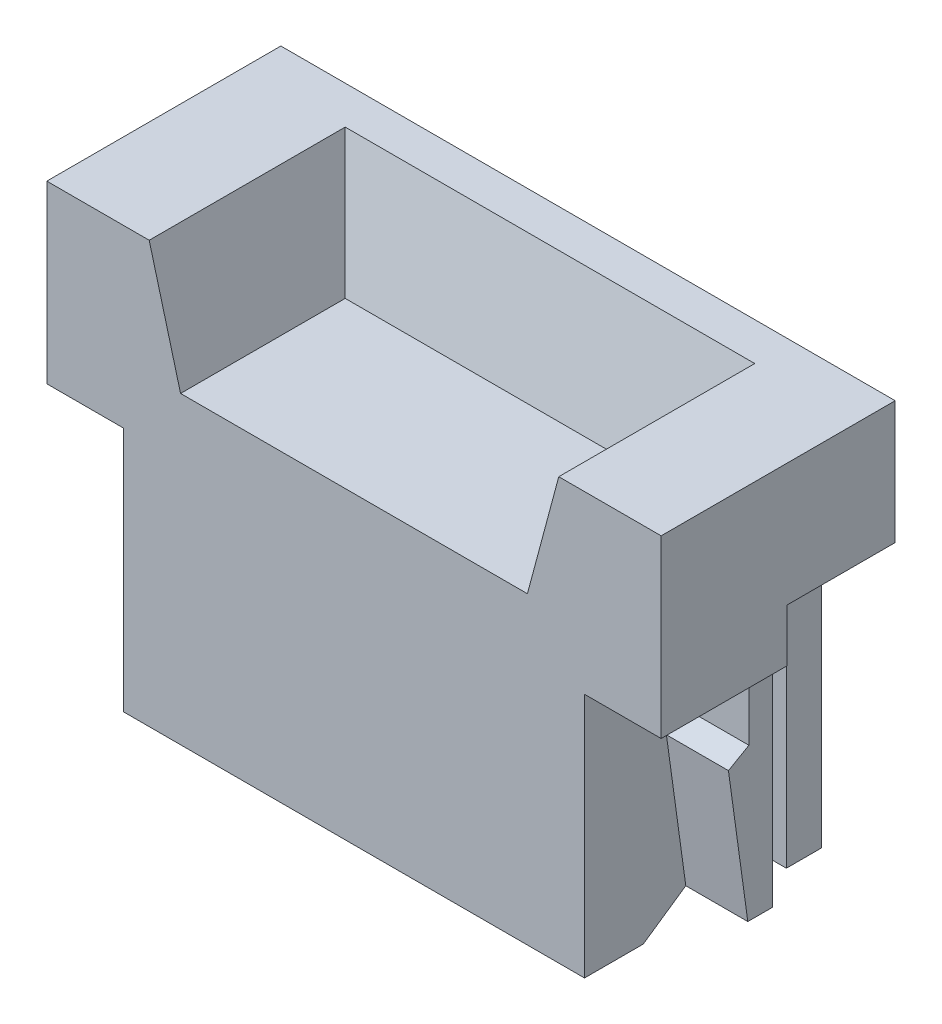
SolidWorks part; units mm, degrees
ref_plane "Front Plane" through (0, 0, 0) normal (0, 0, 1) x (1, 0, 0)
ref_plane "Top Plane" through (0, 0, 0) normal (0, 1, 0) x (1, 0, 0)
ref_plane "Right Plane" through (0, 0, 0) normal (1, 0, 0) x (0, 0, -1)
sketch "Sketch1" plane through (0, 0, 0) normal (1, 0, 0) x (0, 0, -1)
  line L0 (76.1908, 253.9388) -> (293.5266, 253.9388) construction
  line L1 (23.1526, 131.5086) -> (115.714, 131.5086) construction
  line L2 (4, 7.1) -> (1.0928, 7.1)
  line L3 (0, 0) -> (4, 0) construction
  line L4 (0, 0) -> (0, 7.1) construction
  line L5 (0, 7.1) -> (4, 7.1) construction
  line L6 (4, 0) -> (4, 7.1) construction
  line L7 (1.0928, 7.1) -> (1.0928, 6.4991)
  line L8 (1.0928, 6.4991) -> (0, 6.4991)
  line L9 (0, 6.4991) -> (0, 0)
  line L10 (0, 0) -> (1.0042, 0)
  line L11 (1.0042, 0) -> (1.7309, 0.4997)
  line L12 (1.7309, 0.4997) -> (3.45, 0.4997)
  line L13 (3.45, 0.4997) -> (3.45, 5.8996)
  line L14 (3.45, 5.8996) -> (4, 5.8996)
  line L15 (4, 5.8996) -> (4, 7.1)
  point P9 (1.0042, 0)
  point P18 (1.7006, 0.4997)
  dimension "D1" = 7.1
  dimension "D2" = 4
  dimension "D3" = 1.2004
  dimension "D4" = 3.45
  dimension "D5" = 5.3998
  dimension "D6" = 1.0042
  dimension "D7" = 1.7191
  dimension "D8" = 2.9072
  dimension "D9" = 0.6009
extrude "Boss-Extrude1" add sketch "Sketch1" along normal mid plane 10
sketch "Sketch2" plane through (0, 7.1, 0) normal (0, 1, 0) x (1, 0, 0)
  line L0 (-6, 4) -> (-4.54, 4)
  line L1 (5, 4) -> (-5, 4) construction
  line L2 (-4.54, 4) -> (-4.54, 2.85)
  line L3 (-4.54, 2.85) -> (-3.94, 2.85)
  line L4 (-3.94, 2.85) -> (-3.94, 2.15)
  line L5 (-3.94, 2.15) -> (-5, 2.15)
  line L6 (-5, 4) -> (-5, 1.0928) construction
  line L7 (-5, 2.15) -> (-5, 1.75)
  line L8 (-5, 1.75) -> (-3.94, 1.75)
  line L9 (-3.94, 1.75) -> (-3.94, 0)
  line L10 (5, 0) -> (-5, 0) construction
  line L11 (-3.94, 0) -> (-6, 0)
  line L12 (-6, 0) -> (-6, 4)
  line L13 (5, 3.45) -> (-5, 3.45) construction
  line L14 (0, 0) -> (0, 4) construction
  line L15 (6, 0) -> (6, 4)
  line L16 (3.94, 0) -> (6, 0)
  line L17 (3.94, 1.75) -> (3.94, 0)
  line L18 (5, 1.75) -> (3.94, 1.75)
  line L19 (5, 2.15) -> (5, 1.75)
  line L20 (3.94, 2.15) -> (5, 2.15)
  line L21 (3.94, 2.85) -> (3.94, 2.15)
  line L22 (4.54, 2.85) -> (3.94, 2.85)
  line L23 (4.54, 4) -> (4.54, 2.85)
  line L24 (6, 4) -> (4.54, 4)
  dimension "D1" = 4.54
  dimension "D2" = 3.94
  dimension "D3" = 1.75
  dimension "D4" = 1
  dimension "D5" = 0.4
  dimension "D6" = 0.6
extrude "Cut-Extrude1" cut sketch "Sketch2" against normal through all
sketch "Sketch3" plane through (0, 0.4997, 0) normal (0, -1, 0) x (1, 0, 0)
  line L0 (4.54, -3.45) -> (-4.54, -3.45) construction
  line L1 (-0.45, -1.9) -> (0.45, -1.9)
  line L2 (-0.45, -1.9) -> (-0.45, -2.8)
  line L3 (-0.45, -2.8) -> (0.45, -2.8)
  line L4 (0.45, -1.9) -> (0.45, -2.8)
  line L5 (2.05, -1.9) -> (2.05, -2.8)
  line L6 (2.05, -1.9) -> (2.95, -1.9)
  line L7 (2.95, -1.9) -> (2.95, -2.8)
  line L8 (2.05, -2.8) -> (2.95, -2.8)
  line L9 (-2.95, -1.9) -> (-2.95, -2.8)
  line L10 (-2.95, -1.9) -> (-2.05, -1.9)
  line L11 (-2.05, -1.9) -> (-2.05, -2.8)
  line L12 (-2.95, -2.8) -> (-2.05, -2.8)
  point P6 (0, -2.8)
  dimension "D1" = 0.65
  dimension "D2" = 0.9
  dimension "D5" = 2.5
  dimension "D6" = 2.5
  dimension "D3" = 2
  dimension "D4" = 2
extrude "Cut-Extrude2" cut sketch "Sketch3" against normal through all
sketch "Sketch4" plane through (3.94, 0, 0) normal (1, 0, 0) x (0, 0, -1)
  line L0 (1.75, 0.4997) -> (1.7309, 0.4997)
  line L1 (1.7309, 0.4997) -> (1.4, 2.8997)
  line L2 (1.4, 2.8997) -> (1.75, 3.0997)
  line L3 (1.75, 0.4997) -> (1.75, 7.1) construction
  line L4 (1.75, 3.0997) -> (1.75, 0.4997)
  line L5 (2.15, 7.1) -> (2.15, 0.4997) construction
  point P10 (1.4, 2.8872)
  dimension "D1" = 0.75
  dimension "D2" = 2.6
  dimension "D3" = 2.4
extrude "Boss-Extrude2" add sketch "Sketch4" along normal through all and the other way through all
sketch "Sketch5" plane through (0, 0.4997, 0) normal (0, -1, 0) x (1, 0, 0)
  line L0 (-1.55, -3.45) -> (-1.25, -3.15)
  line L1 (4.54, -3.45) -> (-4.54, -3.45) construction
  line L2 (-1.25, -3.15) -> (-0.95, -3.45)
  line L3 (-0.95, -3.45) -> (-1.55, -3.45)
  line L8 (0, 0) -> (0, -3.45) construction
  line L9 (0.95, -3.45) -> (1.55, -3.45)
  line L10 (1.25, -3.15) -> (0.95, -3.45)
  line L11 (1.55, -3.45) -> (1.25, -3.15)
  dimension "D1" = 2.5
  dimension "D2" = 0.6
extrude "Cut-Extrude3" cut sketch "Sketch5" against normal up to surface (5.3998 mm away) up to face at (0, 5.8996, -3.725)
sketch "Sketch6" plane through (0, 7.1, 0) normal (0, 1, 0) x (1, 0, 0)
  line L0 (4.54, 4) -> (-4.54, 4) construction
  line L1 (5, 4) -> (-5, 4)
  line L2 (5, 4) -> (5, 0)
  line L3 (5, 0) -> (-5, 0)
  line L4 (-5, 4) -> (-5, 0)
  point P4 (5.1362, 4.2959)
extrude "Boss-Extrude3" add sketch "Sketch6" against normal blind 2 and the other way blind 0.1
sketch "Sketch7" plane through (0, 7.2, 0) normal (0, 1, 0) x (1, 0, 0)
  line L1 (-2.95, 2.8) -> (2.95, 2.8) construction
  line L2 (-2.95, 2.8) -> (-2.95, 1.9) construction
  line L3 (-2.95, 1.9) -> (2.95, 1.9) construction
  line L4 (2.95, 2.8) -> (2.95, 1.9) construction
  line L8 (-3.5, 3.35) -> (-2.05, 1.9) construction
  line L9 (-3.5, 3.35) -> (3.5, 3.35)
  line L10 (-3.5, 3.35) -> (-3.5, 1.35)
  line L11 (-3.5, 1.35) -> (3.5, 1.35)
  line L12 (3.5, 3.35) -> (3.5, 1.35)
  point P4 (0, 3.35)
  point P6 (-2.05, 1.9)
  point P12 (-3.5, 2.35)
  point P13 (-2.95, 2.35)
  point P15 (0, 0)
  dimension "D2" = 2
extrude "Cut-Extrude4" cut sketch "Sketch7" against normal blind 2 draft 15
sketch "Sketch8" plane through (0, 0, 0) normal (0, 0, 1) x (1, 0, 0)
  line L4 (-2.9641, 5.2) -> (2.9641, 5.2)
  line L5 (-3.5, 7.2) -> (-2.9641, 5.2)
  line L6 (3.5, 7.2) -> (-3.5, 7.2)
  line L7 (2.9641, 5.2) -> (3.5, 7.2)
  line L9 (-3.5, 7.2) -> (-2.9641, 5.2)
  line L10 (3.5, 7.2) -> (-3.5, 7.2)
  line L11 (2.9641, 5.2) -> (3.5, 7.2)
  line L12 (-2.9641, 5.2) -> (2.9641, 5.2)
  dimension "D1" = 0
extrude "Cut-Extrude5" cut sketch "Sketch8" against normal up to surface (1.35 mm away) up to face at (0, 6.2, -1.6179)
sketch "Sketch9" plane through (0, 5.1, 0) normal (0, -1, 0) x (1, 0, 0)
  line L0 (-5, -1.75) -> (-3.94, -1.75) construction
  line L1 (-3.94, -1.75) -> (-3.94, 0) construction
  line L2 (-3.94, 0) -> (-5, 0) construction
  line L3 (-5, 0) -> (-5, -1.75) construction
  line L4 (3.94, 0) -> (3.94, -1.75) construction
  line L5 (3.94, -1.75) -> (5, -1.75) construction
  line L6 (5, -1.75) -> (5, 0) construction
  line L7 (5, 0) -> (3.94, 0) construction
  line L8 (-5, -1.75) -> (-3.94, -1.75)
  line L9 (-3.94, -1.75) -> (-3.94, 0)
  line L10 (-3.94, 0) -> (-5, 0)
  line L11 (-5, 0) -> (-5, -1.75)
  line L12 (3.94, 0) -> (3.94, -1.75)
  line L13 (3.94, -1.75) -> (5, -1.75)
  line L14 (5, -1.75) -> (5, 0)
  line L15 (5, 0) -> (3.94, 0)
extrude "Boss-Extrude4" add sketch "Sketch9" along normal blind 0.9
ref_axis "Axis1" through (5, 7.2, 0) along (-1, 0, 0)
ref_point "Point2"
sketch "Sketch10" plane through (5, 0, 0) normal (1, 0, 0) x (0, 0, -1)
  line L0 (0, 4.2) -> (2.15, 4.2)
  line L1 (2.15, 0.4997) -> (2.15, 5.1) construction
  line L2 (2.15, 4.2) -> (2.15, 5.1)
  line L3 (2.15, 5.1) -> (4, 5.1)
  line L4 (4, 5.1) -> (4, 7.2)
  line L5 (4, 7.2) -> (4, 5.1) construction
  line L6 (4, 7.2) -> (0, 7.2)
  line L7 (0, 7.2) -> (0, 4.2)
extrude "Boss-Extrude5" add sketch "Sketch10" along normal offset from surface (0.25 mm away) 5.25 up to plane "Right Plane"
extrude "Boss-Extrude6" add sketch "Sketch10<2>" against normal offset from surface (0.25 mm away) 10.5 from surface up to face at (5.25, 5.5, -2.05) starting at face at (-5, 3.9999, -1.8931)
sketch "Sketch10<2>" plane through (5, 0, 0) normal (1, 0, 0) x (0, 0, -1) same geometry as "Sketch10"
